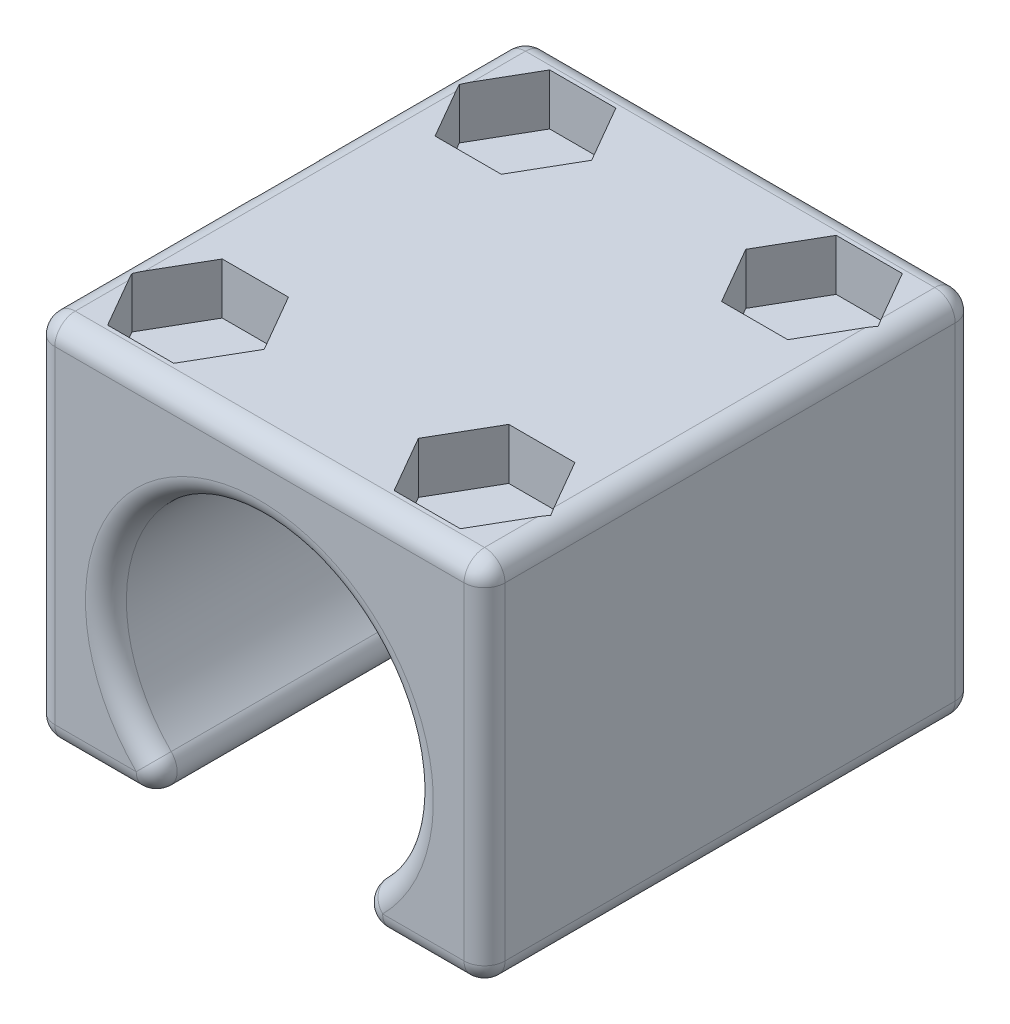
SolidWorks part; units mm, degrees
material "Alliage 1060"
ref_plane "Plan de face" through (0, 0, 0) normal (0, 0, 1) x (1, 0, 0)
ref_plane "Plan de dessus" through (0, 0, 0) normal (0, 1, 0) x (1, 0, 0)
ref_plane "Plan de droite" through (0, 0, 0) normal (1, 0, 0) x (0, 0, -1)
sketch "Esquisse1" plane through (0, 0, 0) normal (0, 0, 1) x (1, 0, 0)
  line L0 (0, 0) -> (0, -2) construction
  line L1 (11, -9) -> (2.6926, -9)
  line L2 (11, -9) -> (11, 9)
  line L3 (11, 9) -> (-11, 9)
  line L4 (-11, -9) -> (-11, 9)
  line L5 (11, -9) -> (-11, 9) construction
  line L6 (11, 9) -> (-11, -9) construction
  line L7 (2.6926, -9) -> (-2.6926, -9) construction
  line L8 (-2.6926, -9) -> (-11, -9)
  arc A1 (2.6926, -9) -> (-2.6926, -9) centre (0, -2) ccw
  arc A2 (-2.6926, -9) -> (2.6926, -9) centre (0, -2) ccw construction
  point P0 (0, 0)
  dimension "D2" = 2
  dimension "D4" = 15
  dimension "D1" = 11
  dimension "D3" = 11
extrude "Boss.-Extru.1" add sketch "Esquisse1" along normal blind 12 and the other way blind 12
sketch "Esquisse2" plane through (0, 0, 0) normal (0, 1, 0) x (1, 0, 0)
  line L0 (-3.7668, -8) -> (-5.3834, -5.2)
  line L1 (7, -8) -> (-7, -8) construction
  line L2 (7, -8) -> (7, 8) construction
  line L3 (7, 8) -> (-7, 8) construction
  line L4 (-7, -8) -> (-7, 8) construction
  line L5 (7, -8) -> (-7, 8) construction
  line L6 (7, 8) -> (-7, -8) construction
  line L7 (-5.3834, -5.2) -> (-8.6166, -5.2)
  line L8 (-8.6166, -5.2) -> (-10.2332, -8)
  line L9 (-3.7668, 8) -> (-5.3834, 10.8)
  line L10 (-5.3834, 10.8) -> (-8.6166, 10.8)
  line L11 (-8.6166, 10.8) -> (-10.2332, 8)
  line L12 (-10.2332, 8) -> (-8.6166, 5.2)
  line L13 (-8.6166, 5.2) -> (-5.3834, 5.2)
  line L14 (-5.3834, 5.2) -> (-3.7668, 8)
  line L15 (-10.2332, -8) -> (-8.6166, -10.8)
  line L16 (-8.6166, -10.8) -> (-5.3834, -10.8)
  line L17 (-5.3834, -10.8) -> (-3.7668, -8)
  line L19 (0, 8) -> (0, 0) construction
  line L20 (5.3834, -10.8) -> (3.7668, -8)
  line L21 (8.6166, -10.8) -> (5.3834, -10.8)
  line L22 (10.2332, -8) -> (8.6166, -10.8)
  line L23 (8.6166, -5.2) -> (10.2332, -8)
  line L24 (5.3834, -5.2) -> (8.6166, -5.2)
  line L25 (3.7668, -8) -> (5.3834, -5.2)
  line L26 (5.3834, 5.2) -> (3.7668, 8)
  line L27 (8.6166, 5.2) -> (5.3834, 5.2)
  line L28 (10.2332, 8) -> (8.6166, 5.2)
  line L29 (8.6166, 10.8) -> (10.2332, 8)
  line L30 (5.3834, 10.8) -> (8.6166, 10.8)
  line L31 (3.7668, 8) -> (5.3834, 10.8)
  line L32 (-7, -24) -> (-7, -8) construction
  circle A4 centre (-7, 8) radius 2.8 construction
  circle A5 centre (7, 8) radius 2.8 construction
  point P0 (0, 0)
  dimension "D3" = 5.6
  dimension "D4" = 2
  dimension "D1" = 14
  dimension "D2" = 16
extrude "Enlèv. mat.-Extru.1" cut sketch "Esquisse2" against normal blind 2.5 from surface starting at face at (0, 9, 0)
fillet "Congé1" radius 1 18 edges at (-11, 9, 0) (-11, -9, 0) (-6.8463, -9, -12) (0, 5.5, -12) (6.8463, -9, -12) (0, 9, -12) (-11, 0, -12) (11, 0, -12) (11, -9, 0) (11, 9, 0) (0, 9, 12) (11, 0, 12) (6.8463, -9, 12) (0, 5.5, 12) (-6.8463, -9, 12) (-11, 0, 12) (2.6926, -9, 0) (-2.6926, -9, 0)
sketch "Esquisse3" plane through (-11, 0, 0) normal (-1, 0, 0) x (0, 0, 1)
  line L0 (0, 6) -> (0, -6) construction
  line L2 (3.2332, 6) -> (1.6166, 8.8)
  line L3 (1.6166, 8.8) -> (-1.6166, 8.8)
  line L4 (-1.6166, 8.8) -> (-3.2332, 6)
  line L5 (-3.2332, 6) -> (-1.6166, 3.2)
  line L6 (-1.6166, 3.2) -> (1.6166, 3.2)
  line L7 (1.6166, 3.2) -> (3.2332, 6)
  line L8 (3.2332, -6) -> (1.6166, -3.2)
  line L9 (1.6166, -3.2) -> (-1.6166, -3.2)
  line L10 (-1.6166, -3.2) -> (-3.2332, -6)
  line L11 (-3.2332, -6) -> (-1.6166, -8.8)
  line L12 (-1.6166, -8.8) -> (1.6166, -8.8)
  line L13 (1.6166, -8.8) -> (3.2332, -6)
  circle A2 centre (0, 6) radius 2.8 construction
  circle A3 centre (0, -6) radius 2.8 construction
  dimension "D3" = 5.6
  dimension "D4" = 5.6
  dimension "D1" = 12
extrude "Enlèv. mat.-Extru.2" cut sketch "Esquisse3" against normal blind 2.5
